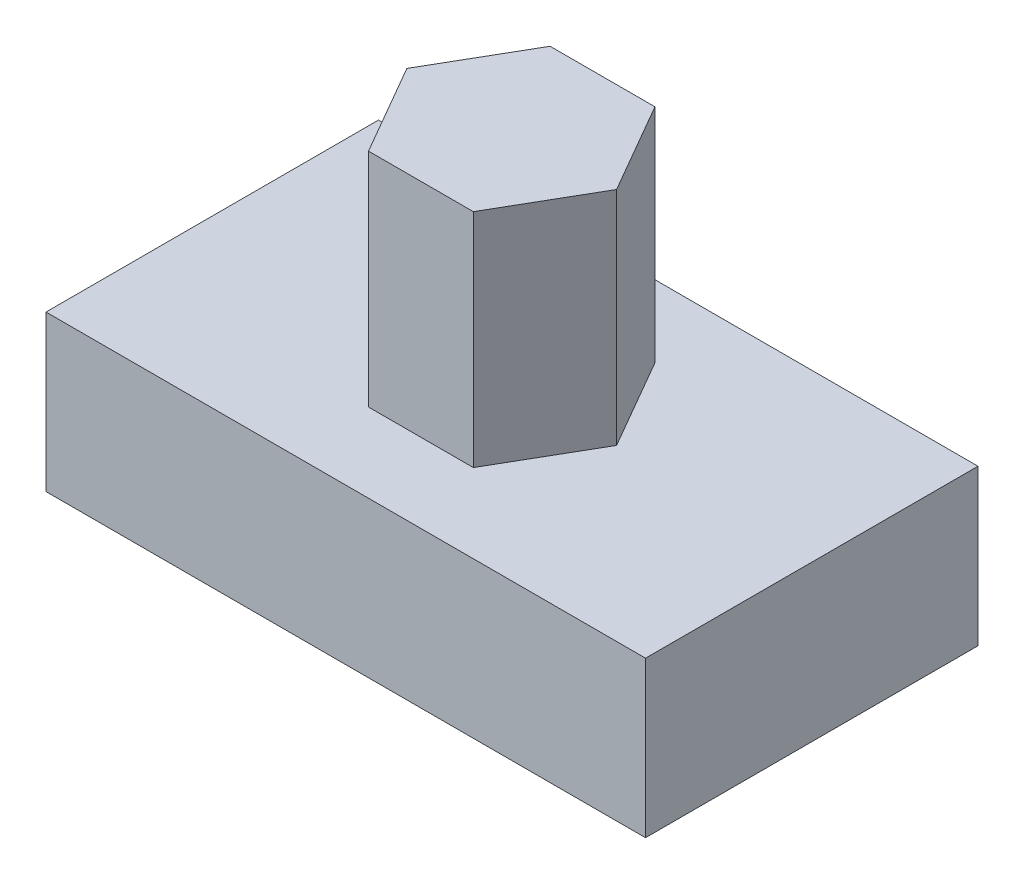
SolidWorks part; units mm, degrees
ref_plane "Front Plane" through (0, 0, 0) normal (0, 0, 1) x (1, 0, 0)
ref_plane "Top Plane" through (0, 0, 0) normal (0, 1, 0) x (1, 0, 0)
ref_plane "Right Plane" through (0, 0, 0) normal (1, 0, 0) x (0, 0, -1)
sketch "Sketch1" plane through (0, 0, 0) normal (0, 0, 1) x (1, 0, 0)
  line L1 (-68.7035, -17.821) -> (68.7035, -17.821)
  line L2 (-68.7035, -17.821) -> (-68.7035, 17.821)
  line L3 (-68.7035, 17.821) -> (68.7035, 17.821)
  line L4 (68.7035, -17.821) -> (68.7035, 17.821)
  line L5 (-68.7035, -17.821) -> (68.7035, 17.821) construction
  line L6 (-68.7035, 17.821) -> (68.7035, -17.821) construction
  point P0 (0, 0)
extrude "Boss-Extrude1" add sketch "Sketch1" along normal blind 76.2 contours L1 L4 L3 L2
sketch "Sketch2" plane through (0, 17.821, 0) normal (0, 1, 0) x (1, 0, 0)
  line L1 (23.159, -37.2907) -> (11.1437, -16.4796)
  line L2 (11.1437, -16.4796) -> (-12.8869, -16.4796)
  line L3 (-12.8869, -16.4796) -> (-24.9022, -37.2907)
  line L4 (-24.9022, -37.2907) -> (-12.8869, -58.1018)
  line L5 (-12.8869, -58.1018) -> (11.1437, -58.1018)
  line L6 (11.1437, -58.1018) -> (23.159, -37.2907)
  circle A0 centre (-0.8716, -37.2907) radius 20.8111 construction
extrude "Boss-Extrude2" add sketch "Sketch2" along normal blind 50.8
